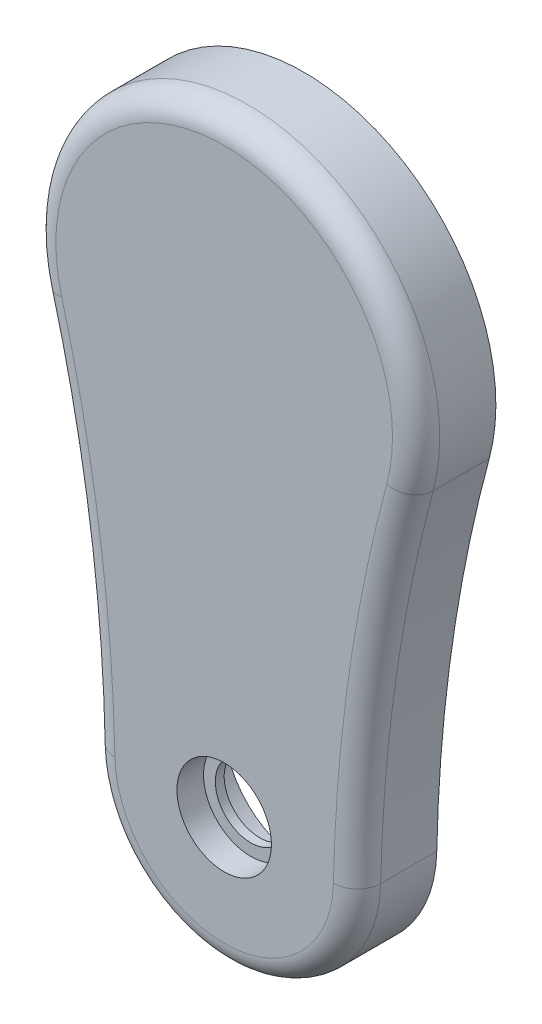
SolidWorks part; units mm, degrees
note: The reader was unsure of these and kept them because the rebuilt part matched: shared geometry of "Эскиз3<3>", "Эскиз3<4>", "Эскиз3<5>", "Эскиз3<6>".
ref_plane "Front" through (0, 0, 0) normal (0, 0, 1) x (1, 0, 0)
ref_plane "Top" through (0, 0, 0) normal (0, 1, 0) x (1, 0, 0)
ref_plane "Right" through (0, 0, 0) normal (1, 0, 0) x (0, 0, -1)
sketch "Эскиз2" plane through (0, 0, 0) normal (0, 0, 1) x (1, 0, 0)
  line L0 (0, 0) -> (0, 79)
  line L2 (0, 79) -> (0, 125)
  circle A1 centre (0, 125) radius 32.5
  circle A2 centre (0, 55) radius 22.5
  arc A3 (-22.4948, 54.5164) -> (-31.3816, 116.5476) centre (-282.4347, 48.9286) ccw
  arc A4 (31.3816, 116.5476) -> (22.4948, 54.5164) centre (282.4347, 48.9286) ccw
  circle A5 centre (0, 125) radius 23.5
  arc A9 (-13.4969, 54.7099) -> (-22.6913, 118.8883) centre (-282.4347, 48.9286) ccw
  arc A10 (22.6913, 118.8883) -> (13.4969, 54.7099) centre (282.4347, 48.9286) ccw
  circle A11 centre (0, 55) radius 13.5
  point P11 (572.8347, 59.25)
  point P18 (-293.4288, 61.4643)
  point P19 (-33.6762, 138.4827)
  point P20 (293.4288, 61.4643)
  point P21 (551.9933, 138.4827)
  point P22 (-12.8347, 59.25)
  point P28 (0, 32.5)
  dimension "D2" = 70
  dimension "D3" = 65
  dimension "D4" = 260
  dimension "D5" = 45
  dimension "D7" = 260
  dimension "D8" = 9
  dimension "D9" = 47
  dimension "D6" = 55
  dimension "D12" = 32.5
  dimension "D10" = 9
extrude "Бобышка-Вытянуть2" add sketch "Эскиз2" along normal blind 13.5
sketch "Эскиз3" plane through (0, 0, 0) normal (0, 0, 1) x (1, 0, 0)
  line L0 (0, 0) -> (0, 55)
  line L1 (0, 0) -> (0, 125)
  circle A0 centre (0, 55) radius 6
  circle A1 centre (0, 55) radius 8
  circle A2 centre (0, 55) radius 13.5
  circle A3 centre (0, 125) radius 21
  circle A4 centre (0, 125) radius 23.5
  dimension "D3" = 27
  dimension "D1" = 70
  dimension "D2" = 55
extrude "Вырез-Вытянуть1" cut sketch "Эскиз3" along normal through all contours A0
extrude "Вырез-Вытянуть2" cut sketch "Эскиз3<3>" along normal through all from offset 9 contours A1
sketch "Эскиз3<3>" plane through (0, 0, 0) normal (0, 0, 1) x (1, 0, 0) same geometry as "Эскиз3"
extrude "Вырез-Вытянуть3" cut sketch "Эскиз3<4>" along normal blind 7.5 contours A2
sketch "Эскиз3<4>" plane through (0, 0, 0) normal (0, 0, 1) x (1, 0, 0) same geometry as "Эскиз3"
fillet "Скругление1" radius 4 4 edges at (25.0626, 85.8007, 13.5) (0, 32.5, 13.5) (-25.0626, 85.8007, 13.5) (0, 157.5, 13.5)
extrude "Вырез-Вытянуть5" cut sketch "Эскиз3<5>" along normal blind 10.5
sketch "Эскиз3<5>" plane through (0, 0, 0) normal (0, 0, 1) x (1, 0, 0) same geometry as "Эскиз3"
extrude "Вырез-Вытянуть7" cut sketch "Эскиз3<6>" along normal blind 7 contours A4
sketch "Эскиз3<6>" plane through (0, 0, 0) normal (0, 0, 1) x (1, 0, 0) same geometry as "Эскиз3"
